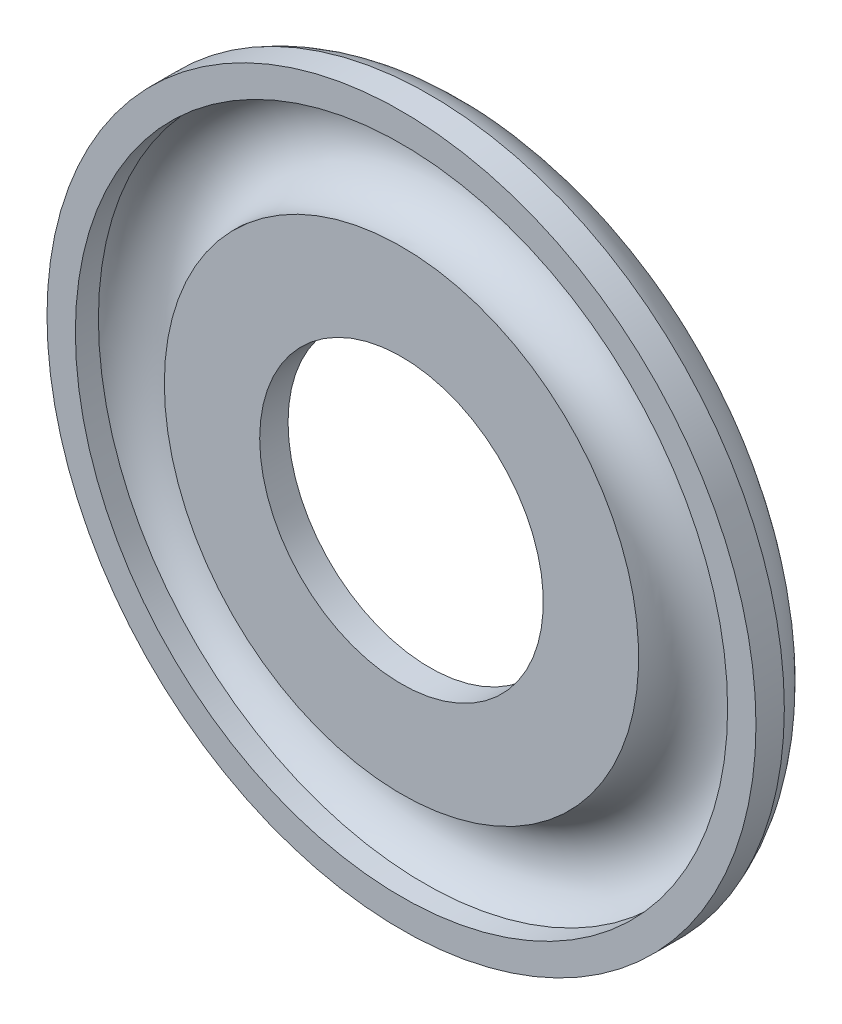
SolidWorks part; units mm, degrees
ref_plane "前视基准面" through (0, 0, 0) normal (0, 0, 1) x (1, 0, 0)
ref_plane "上视基准面" through (0, 0, 0) normal (0, 1, 0) x (1, 0, 0)
ref_plane "右视基准面" through (0, 0, 0) normal (1, 0, 0) x (0, 0, -1)
sketch "草图1" plane through (0, 0, 0) normal (0, 0, 1) x (1, 0, 0)
  circle A0 centre (0, 0) radius 12.5
  dimension "D1" = 25
extrude "凸台-拉伸1" add sketch "草图1" along normal blind 1
sketch "草图2" plane through (0, 0, 0) normal (0, 0, -1) x (-1, 0, 0)
  circle A0 centre (0, 0) radius 7.5
  circle A1 centre (0, 0) radius 12.5
  circle A2 centre (0, 0) radius 12.5
  dimension "D2" = 5
  dimension "D1" = 0
sketch "草图3" plane through (0, 0, 0) normal (0, 1, 0) x (1, 0, 0)
  line L2 (-12.5, 0) -> (-7.5, 0)
  arc A0 (-12.5, 0) -> (-7.5, 0) centre (-10, -0.8592) cw
  dimension "D1" = 2.6435
  dimension "D2" = 5
sweep "扫描1" add profiles "草图3" path "草图2"
shell "抽壳1" thickness 1 removed face at (12.5, 0, 1)
sketch "草图4" plane through (0, 0, 0) normal (0, 0, -1) x (-1, 0, 0)
  circle A0 centre (0, 0) radius 5
  dimension "D1" = 10
extrude "切除-拉伸1" cut sketch "草图4" against normal through all both and the other way through all
